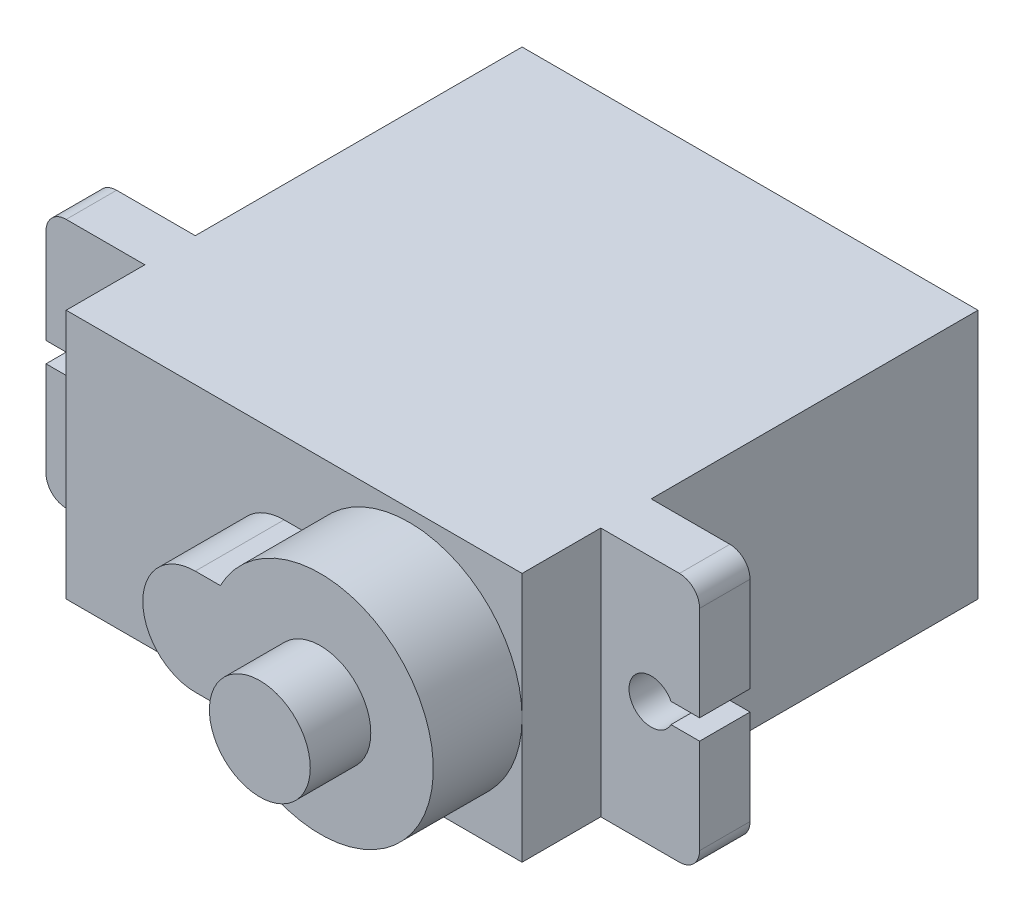
SolidWorks part; units mm, degrees
ref_plane "Front Plane" through (0, 0, 0) normal (0, 0, 1) x (1, 0, 0)
ref_plane "Top Plane" through (0, 0, 0) normal (0, 1, 0) x (1, 0, 0)
ref_plane "Right Plane" through (0, 0, 0) normal (1, 0, 0) x (0, 0, -1)
sketch "Sketch1" plane through (0, 0, 0) normal (0, 0, 1) x (1, 0, 0)
  line L1 (-11.3, 6.2) -> (11.3, 6.2)
  line L2 (-11.3, 6.2) -> (-11.3, -6.2)
  line L3 (-11.3, -6.2) -> (11.3, -6.2)
  line L4 (11.3, 6.2) -> (11.3, -6.2)
  line L5 (-11.3, 6.2) -> (11.3, -6.2) construction
  line L6 (-11.3, -6.2) -> (11.3, 6.2) construction
  point P0 (0, 0)
  dimension "D1" = 12.4
  dimension "D2" = 22.6
extrude "Boss-Extrude1" add sketch "Sketch1" along normal blind 22.6
sketch "Sketch2" plane through (0, 0, 0) normal (1, 0, 0) x (0, 0, -1)
  line L0 (-22.6, 6.2) -> (0, 6.2) construction
  line L1 (-18.7, 6.2) -> (-16.2, 6.2)
  line L2 (-18.7, 6.2) -> (-18.7, -6.2)
  line L3 (-18.7, -6.2) -> (-16.2, -6.2)
  line L4 (-16.2, 6.2) -> (-16.2, -6.2)
  line L5 (-22.6, -6.2) -> (0, -6.2) construction
  line L6 (-22.6, -6.2) -> (-22.6, 6.2) construction
  dimension "D1" = 2.5
  dimension "D2" = 6.4
extrude "Boss-Extrude2" add sketch "Sketch2" along normal mid plane 32.4
sketch "Sketch3" plane through (0, 0, 18.7) normal (0, 0, 1) x (1, 0, 0)
  line L0 (0, 0) -> (-13.8, 0) construction
  line L1 (0, 0) -> (0, 6.2) construction
  line L2 (11.3, 6.2) -> (-11.3, 6.2) construction
  line L3 (-16.2, 6.2) -> (-16.2, -6.2) construction
  line L4 (-16.2, 0.5) -> (-14.7798, 0.5)
  line L5 (-16.2, 0.5) -> (-16.2, -0.5)
  line L6 (-16.2, -0.5) -> (-14.7798, -0.5)
  line L7 (-16.2, 0.5) -> (-14.7798, 0.5)
  line L8 (-16.2, 0) -> (-13.8, 0) construction
  line L9 (-16.2, -0.5) -> (-14.7798, -0.5)
  line L10 (16.2, 0.5) -> (14.7798, 0.5)
  line L11 (16.2, 0.5) -> (16.2, -0.5)
  line L12 (16.2, -0.5) -> (14.7798, -0.5)
  arc A0 (-14.7798, -0.5) -> (-14.7798, 0.5) centre (-13.8, 0) ccw
  arc A1 (14.7798, -0.5) -> (14.7798, 0.5) centre (13.8, 0) cw
  line M10 (-16.2, 6.2) -> (-16.2, -6.2)
  dimension "D1" = 2.2
  dimension "D2" = 13.8
  dimension "D3" = 1
extrude "Cut-Extrude1" cut sketch "Sketch3" against normal through all contours L6 A0 L4 M10 | A1 L10 L11 L12 region at (-14.2507, 0, 18.7)
sketch "Sketch4" plane through (0, 0, 22.6) normal (0, 0, 1) x (1, 0, 0)
  line L0 (11.3, 6.2) -> (11.3, -6.2) construction
  line L3 (0, 0) -> (-0.5, 0) construction
  line L4 (-3.1, 2.949) -> (-3.1, -2.3492) construction
  line L5 (11.3, -6.2) -> (11.3, 6.2) construction
  line L6 (-0.5, 0) -> (5.7, 0) construction
  line L7 (-0.5, 2.6) -> (0.7402, 2.6)
  line L8 (-0.5, -2.6) -> (0.7402, -2.6)
  arc A0 (0.7402, -2.6) -> (0.7402, 2.6) centre (5.7, 0) ccw
  arc A1 (-0.5, 2.6) -> (-0.5, -2.6) centre (-0.5, 0) ccw
  dimension "D2" = 5.2
  dimension "D3" = 11.2
  dimension "D1" = 14.4
extrude "Boss-Extrude3" add sketch "Sketch4" along normal offset from surface (4.4 mm away) 27 up to face at (0, 0, 0)
sketch "Sketch5" plane through (0, 0, 27) normal (0, 0, 1) x (1, 0, 0)
  circle A0 centre (5.7, 0) radius 2.5
  arc A1 (11.3, 0) -> (0.7402, 2.6) centre (5.7, 0) ccw construction
  dimension "D1" = 5
extrude "Boss-Extrude4" add sketch "Sketch5" along normal offset from surface (3 mm away) 30 up to face at (0, 0, 0)
fillet "Fillet1" radius 1 4 edges at (-16.2, 6.2, 17.45) (16.2, 6.2, 17.45) (16.2, -6.2, 17.45) (-16.2, -6.2, 17.45)
ref_axis "Axis1" through (5.7, 0, 30) along (0, 0, -1)
